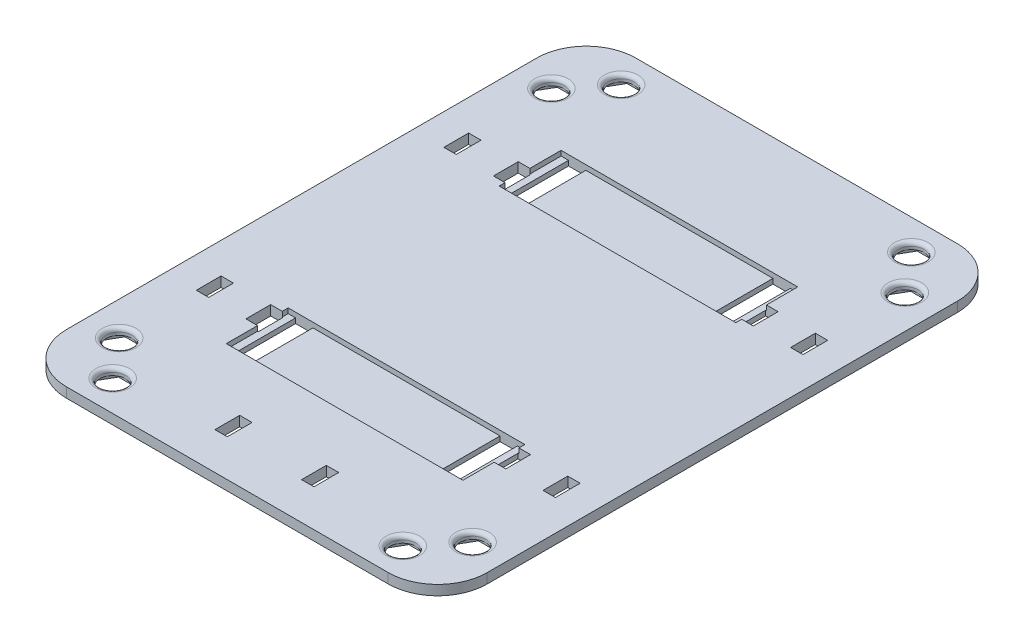
SolidWorks part; units mm, degrees
material "3-D Printed ABS"
ref_plane "Front Plane" through (0, 0, 0) normal (0, 0, 1) x (1, 0, 0)
ref_plane "Top Plane" through (0, 0, 0) normal (0, 1, 0) x (1, 0, 0)
ref_plane "Right Plane" through (0, 0, 0) normal (1, 0, 0) x (0, 0, -1)
sketch "Sketch1" plane through (0, 0, 0) normal (0, 1, 0) x (1, 0, 0)
  line L1 (-53.975, -73.025) -> (53.975, -73.025)
  line L2 (-53.975, -73.025) -> (-53.975, 73.025)
  line L3 (-53.975, 73.025) -> (53.975, 73.025)
  line L4 (53.975, -73.025) -> (53.975, 73.025)
  line L5 (-53.975, -73.025) -> (53.975, 73.025) construction
  line L6 (-53.975, 73.025) -> (53.975, -73.025) construction
  point P0 (0, 0)
  dimension "D1" = 107.95
  dimension "PlateY" = 146.05
extrude "Boss-Extrude1" add sketch "Sketch1" against normal blind 2.54
sketch "Sketch2" plane through (0, 0, 0) normal (0, 1, 0) x (1, 0, 0)
  line L0 (0, 0) -> (152.4, 0) construction
  line L1 (0, 0) -> (0, 152.4) construction
  line L4 (0, 0) -> (-53.975, 73.025) construction
  line L5 (0, 0) -> (-152.4, 0) construction
  line L6 (0, 0) -> (-152.4, 152.4) construction
  line L7 (-53.975, 73.025) -> (-53.975, -73.025) construction
  line L8 (53.975, 73.025) -> (-53.975, 73.025) construction
  line L9 (-152.4, 152.4) -> (-41.275, 60.325) construction
  line L10 (-41.275, 60.325) -> (0, 26.1257) construction
  line L11 (-30.7521, 73.025) -> (-53.975, 44.9974) construction
  circle A0 centre (-37.2189, 65.2108) radius 3.302
  circle A1 centre (45.3264, 55.4354) radius 3.302
  circle A2 centre (37.2189, 65.2108) radius 3.302
  circle A3 centre (-45.3264, -55.4354) radius 3.302
  circle A4 centre (-45.3264, 55.4354) radius 3.302
  circle A5 centre (-37.2189, -65.2108) radius 3.302
  circle A6 centre (37.2189, -65.2108) radius 3.302
  circle A7 centre (45.3264, -55.4354) radius 3.302
  point P12 (-41.275, 60.325)
  point P15 (-37.2189, 65.2108)
  dimension "D1" = 6.604
  dimension "D3" = 12.7
  dimension "D8" = 6.604
  dimension "D2" = 12.7
  dimension "D4" = 152.4
  dimension "D5" = 152.4
  dimension "D6" = 152.4
  dimension "D7" = 6.35
  dimension "D9" = 6.35
extrude "Cut-Extrude1" cut sketch "Sketch2" against normal through all
sketch "Sketch3" plane through (0, 0, 0) normal (0, 1, 0) x (1, 0, 0)
  line L0 (-53.975, 0) -> (53.975, 0) construction
  line L1 (-28.445, 42.9374) -> (-24, 42.9374)
  line L2 (-28.445, 42.9374) -> (-28.445, 27.0624)
  line L3 (-28.445, 27.0624) -> (-24, 27.0624)
  line L4 (-24, 42.9374) -> (-24, 27.0624)
  line L5 (24, 42.9374) -> (24, 27.0624)
  line L6 (28.445, 27.0624) -> (24, 27.0624)
  line L7 (28.445, 42.9374) -> (28.445, 27.0624)
  line L8 (28.445, 42.9374) -> (24, 42.9374)
  line L9 (-53.975, 73.025) -> (-53.975, -73.025) construction
  line L10 (53.975, -73.025) -> (53.975, 73.025) construction
  line L11 (0, -34.9999) -> (0, 79.6704) construction
  line L12 (0, 34.9999) -> (0, -79.6704) construction
  line L13 (28.445, -42.9374) -> (24, -42.9374)
  line L14 (28.445, -42.9374) -> (28.445, -27.0624)
  line L15 (28.445, -27.0624) -> (24, -27.0624)
  line L16 (24, -42.9374) -> (24, -27.0624)
  line L17 (-24, -42.9374) -> (-24, -27.0624)
  line L18 (-28.445, -27.0624) -> (-24, -27.0624)
  line L19 (-28.445, -42.9374) -> (-28.445, -27.0624)
  line L20 (-28.445, -42.9374) -> (-24, -42.9374)
  line L21 (-28.445, 34.9999) -> (-40.442, 34.9999) construction
  line L22 (-53.975, -73.025) -> (53.975, -73.025) construction
  point P31 (0, -73.025)
  point P32 (-53.975, 0)
  dimension "D1" = 15.875
  dimension "D2" = 4.445
  dimension "D3" = 24
  dimension "D4" = 34.9999
  dimension "D5" = 34.9999
extrude "Cut-Extrude2" cut sketch "Sketch3" against normal through all
fillet "Fillet1" radius 12.7 4 edges at (53.975, -1.27, -73.025) (53.975, -1.27, 73.025) (-53.975, -1.27, 73.025) (-53.975, -1.27, -73.025)
sketch "Sketch4" plane through (0, 0, 0) normal (0, 1, 0) x (1, 0, 0)
  line L0 (0, 0) -> (80.9727, -80.9727) construction
  line L1 (0, 0) -> (-80.9727, -80.9727) construction
  line L2 (69.1118, -51.1513) -> (28.7006, -10.7401)
  line L3 (28.7006, -10.7401) -> (10.7401, -28.7006)
  line L4 (10.7401, -28.7006) -> (51.1513, -69.1118)
  line L5 (51.1513, -69.1118) -> (69.1118, -51.1513)
  line L6 (0, 0) -> (0, -118.7381) construction
  line L7 (0, 0) -> (-98.4177, 0) construction
  line L8 (-51.1513, -69.1118) -> (-69.1118, -51.1513)
  line L9 (-69.1118, -51.1513) -> (-28.7006, -10.7401)
  line L10 (-28.7006, -10.7401) -> (-10.7401, -28.7006)
  line L11 (-10.7401, -28.7006) -> (-51.1513, -69.1118)
  line L12 (-69.1118, 51.1513) -> (-28.7006, 10.7401)
  line L13 (-51.1513, 69.1118) -> (-69.1118, 51.1513)
  line L14 (-10.7401, 28.7006) -> (-51.1513, 69.1118)
  line L15 (-28.7006, 10.7401) -> (-10.7401, 28.7006)
  line L16 (51.1513, 69.1118) -> (69.1118, 51.1513)
  line L17 (69.1118, 51.1513) -> (28.7006, 10.7401)
  line L18 (28.7006, 10.7401) -> (10.7401, 28.7006)
  line L19 (10.7401, 28.7006) -> (51.1513, 69.1118)
  point P6 (19.7204, -19.7204)
  dimension "D1" = 25.4
  dimension "D2" = 57.15
  dimension "D3" = 45
extrude "Cut-Extrude3" [suppressed] cut sketch "Sketch4" against normal blind 1.5875
sketch "Sketch6" [suppressed] plane through (0, 0, 0) normal (0, 1, 0) x (1, 0, 0)
  line L0 (46.3377, -44.1074) -> (34.6634, -32.4331) construction
  line L1 (0, 0) -> (0, -117.7376) construction
  line L2 (0, 0) -> (-151.7285, 0) construction
  line L4 (28.1601, -10.1996) -> (10.1996, -28.1601) construction
  line L5 (50.6107, -68.5712) -> (68.5712, -50.6107) construction
  text T0 "ESC" font "Century Gothic" height in points 22
  dimension "D1" = 45
  dimension "D2" = 20.32
  dimension "D3" = 20.32
extrude "Cut-Extrude5" [suppressed] cut sketch "Sketch6" against normal blind 3.175
sketch "Sketch5" plane through (0, 0, 0) normal (0, 1, 0) x (1, 0, 0)
  line L0 (41.275, 73.025) -> (-41.275, 73.025) construction
  line L1 (14.2875, 15.875) -> (-14.2875, 15.875)
  line L2 (14.2875, 15.875) -> (14.2875, 66.675)
  line L3 (14.2875, 66.675) -> (-14.2875, 66.675)
  line L4 (-14.2875, 15.875) -> (-14.2875, 66.675)
  point P4 (0, 15.875)
  dimension "D1" = 50.8
  dimension "D2" = 28.575
  dimension "D3" = 6.35
extrude "Cut-Extrude4" [suppressed] cut sketch "Sketch5" against normal blind 1.5875
ref_axis "Axis1" through (0, 0.3175, 0) along (0, -1, 0)
pattern_circular "CirPattern1" [suppressed] count 4 over 360 about axis through (0, 0.3175, 0) along (0, -1, 0) of bodies 105
sketch "Sketch7" plane through (0, 0, 0) normal (0, 1, 0) x (1, 0, 0)
  line L0 (0, 0) -> (0, -54.962) construction
  line L1 (63.4018, -13.3522) -> (38.0018, -13.3522)
  line L2 (63.4018, -13.3522) -> (63.4018, 43.7978)
  line L3 (63.4018, 43.7978) -> (38.0018, 43.7978)
  line L4 (38.0018, -13.3522) -> (38.0018, 43.7978)
  line L5 (-38.0018, -13.3522) -> (-38.0018, 43.7978)
  line L6 (-63.4018, 43.7978) -> (-38.0018, 43.7978)
  line L7 (-63.4018, -13.3522) -> (-63.4018, 43.7978)
  line L8 (-63.4018, -13.3522) -> (-38.0018, -13.3522)
  line L9 (-41.275, -73.025) -> (41.275, -73.025) construction
  line L10 (38.5677, -40.64) -> (-18.5823, -40.64)
  line L11 (38.5677, -40.64) -> (38.5677, -66.04)
  line L12 (38.5677, -66.04) -> (-18.5823, -66.04)
  line L13 (-18.5823, -40.64) -> (-18.5823, -66.04)
  line L14 (38.5677, -40.64) -> (-18.5823, -66.04) construction
  line L15 (38.5677, -66.04) -> (-18.5823, -40.64) construction
  line L16 (19.844, -36.1003) -> (-37.306, -36.1003)
  line L17 (19.844, -36.1003) -> (19.844, -61.5003)
  line L18 (19.844, -61.5003) -> (-37.306, -61.5003)
  line L19 (-37.306, -36.1003) -> (-37.306, -61.5003)
  line L20 (19.844, -36.1003) -> (-37.306, -61.5003) construction
  line L21 (19.844, -61.5003) -> (-37.306, -36.1003) construction
  point P11 (9.9927, -53.34)
  point P18 (-8.731, -48.8003)
  dimension "D1" = 57.15
  dimension "D2" = 25.4
  dimension "D3" = 57.15
  dimension "D4" = 25.4
  dimension "D5" = 6.985
  dimension "D6" = 57.15
  dimension "D7" = 25.4
extrude "Cut-Extrude6" [suppressed] cut sketch "Sketch7" against normal blind 1.27
sketch "Sketch8" plane through (0, 0, 0) normal (0, 1, 0) x (1, 0, 0)
  line L7 (19.05, -31.75) -> (-19.05, -31.75)
  line L8 (19.05, -31.75) -> (19.05, 31.75)
  line L9 (19.05, 31.75) -> (-19.05, 31.75)
  line L10 (-19.05, -31.75) -> (-19.05, 31.75)
  point P0 (0, 0)
  dimension "D1" = 38.1
  dimension "D2" = 31.75
  dimension "D3" = 63.5
extrude "Boss-Extrude3" [suppressed] add sketch "Sketch8" along normal blind 2.54
sketch "Sketch11" plane through (0, 0, 0) normal (0, 1, 0) x (1, 0, 0)
  line L0 (-28.445, -42.9374) -> (-24, -42.9374) construction
  line L1 (30.35, -42.9374) -> (-30.35, -42.9374)
  line L2 (30.35, -42.9374) -> (30.35, -27.0624)
  line L3 (30.35, -27.0624) -> (-30.35, -27.0624)
  line L4 (-30.35, -42.9374) -> (-30.35, -27.0624)
  line L5 (28.445, -27.0624) -> (24, -27.0624) construction
  line L6 (28.445, -42.9374) -> (28.445, -27.0624) construction
  line L7 (-28.445, -27.0624) -> (-28.445, -42.9374) construction
  line L8 (0, 0) -> (90.9737, 0) construction
  line L9 (-30.35, 42.9374) -> (-30.35, 27.0624)
  line L10 (30.35, 27.0624) -> (-30.35, 27.0624)
  line L11 (30.35, 42.9374) -> (30.35, 27.0624)
  line L12 (30.35, 42.9374) -> (-30.35, 42.9374)
  dimension "D1" = 1.905
  dimension "D2" = 1.905
extrude "Cut-Extrude9" cut sketch "Sketch11" against normal mid plane 2.54
sketch "Sketch12" plane through (0, 0, 0) normal (0, 1, 0) x (1, 0, 0)
  line L1 (12.7, -51.1354) -> (-12.7, -51.1354)
  line L2 (12.7, -51.1354) -> (12.7, -34.9999)
  line L3 (12.7, -34.9999) -> (-12.7, -34.9999)
  line L4 (-12.7, -51.1354) -> (-12.7, -34.9999)
  line L6 (23.8125, 0) -> (-23.8125, 0) construction
  line L7 (-53.975, 60.325) -> (-53.975, -60.325) construction
  line L9 (-12.7, 51.1354) -> (-12.7, 34.9999)
  line L10 (12.7, 34.9999) -> (-12.7, 34.9999)
  line L11 (12.7, 51.1354) -> (12.7, 34.9999)
  line L12 (12.7, 51.1354) -> (-12.7, 51.1354)
  point P6 (-53.975, 0)
  dimension "D1" = 25.4
  dimension "D2" = 34.9999
extrude "Cut-Extrude12" [suppressed] cut sketch "Sketch12" along normal through all
sketch "Sketch9" plane through (0, 0, 0) normal (0, 1, 0) x (1, 0, 0)
  line L1 (25.1579, -52.4084) -> (-25.6421, -52.4084)
  line L2 (25.1579, -52.4084) -> (25.1579, -1.6084)
  line L3 (25.1579, -1.6084) -> (-25.6421, -1.6084)
  line L4 (-25.6421, -52.4084) -> (-25.6421, -1.6084)
  line L5 (25.1579, -52.4084) -> (-25.6421, -1.6084) construction
  line L6 (25.1579, -1.6084) -> (-25.6421, -52.4084) construction
  point P0 (-0.2421, -27.0084)
  dimension "D1" = 50.8
  dimension "D2" = 50.8
sketch "Sketch13" plane through (0, 0, 0) normal (0, 1, 0) x (1, 0, 0)
  line L0 (0, 0) -> (0, -106.7514) construction
  line L1 (34.925, 3.175) -> (28.575, 3.175)
  line L2 (34.925, 3.175) -> (34.925, -3.175)
  line L3 (34.925, -3.175) -> (28.575, -3.175)
  line L4 (28.575, 3.175) -> (28.575, -3.175)
  line L5 (34.925, 3.175) -> (28.575, -3.175) construction
  line L6 (34.925, -3.175) -> (28.575, 3.175) construction
  line L7 (-34.925, -3.175) -> (-28.575, 3.175) construction
  line L8 (-34.925, 3.175) -> (-28.575, -3.175) construction
  line L9 (-28.575, 3.175) -> (-28.575, -3.175)
  line L10 (-34.925, -3.175) -> (-28.575, -3.175)
  line L11 (-34.925, 3.175) -> (-34.925, -3.175)
  line L12 (-34.925, 3.175) -> (-28.575, 3.175)
  point P0 (31.75, 0)
  point P12 (-31.75, 0)
  dimension "D1" = 6.35
  dimension "D2" = 28.575
  dimension "D3" = 0
extrude "Cut-Extrude13" [suppressed] cut sketch "Sketch13" against normal through all
fillet "Fillet2" radius 1.016 8 edges at (-37.2189, 0, -61.9088) (37.2189, 0, 68.5128) (45.3264, 0, 58.7374) (-37.2189, 0, 61.9088) (-45.3264, 0, 52.1334) (45.3264, 0, -58.7374) (37.2189, 0, -68.5128) (-45.3264, 0, -52.1334)
sketch "Sketch14" plane through (0, 0, 0) normal (0, 1, 0) x (1, 0, 0)
  line L0 (0, 76.698) -> (0, -76.698) construction
  line L1 (33.3248, -34.925) -> (30.1498, -34.925)
  line L2 (33.3248, -34.925) -> (33.3248, -28.575)
  line L3 (33.3248, -28.575) -> (30.1498, -28.575)
  line L4 (30.1498, -34.925) -> (30.1498, -28.575)
  line L5 (0, 0) -> (-92.4571, 0) construction
  line L6 (-30.1498, -34.925) -> (-30.1498, -28.575)
  line L7 (-33.3248, -28.575) -> (-30.1498, -28.575)
  line L8 (-33.3248, -34.925) -> (-33.3248, -28.575)
  line L9 (-33.3248, -34.925) -> (-30.1498, -34.925)
  line L10 (-33.3248, 34.925) -> (-30.1498, 34.925)
  line L11 (-33.3248, 34.925) -> (-33.3248, 28.575)
  line L12 (-33.3248, 28.575) -> (-30.1498, 28.575)
  line L13 (-30.1498, 34.925) -> (-30.1498, 28.575)
  line L14 (30.1498, 34.925) -> (30.1498, 28.575)
  line L15 (33.3248, 28.575) -> (30.1498, 28.575)
  line L16 (33.3248, 34.925) -> (33.3248, 28.575)
  line L17 (33.3248, 34.925) -> (30.1498, 34.925)
  line L18 (-41.275, -73.025) -> (41.275, -73.025) construction
  line L19 (-9.525, -63.5) -> (-9.525, -57.15)
  line L20 (12.7, -63.5) -> (9.525, -63.5)
  line L21 (12.7, -63.5) -> (12.7, -57.15)
  line L22 (12.7, -57.15) -> (9.525, -57.15)
  line L23 (38.1, -73.025) -> (38.1, 73.025) construction
  line L24 (41.275, 73.025) -> (-41.275, 73.025) construction
  line L25 (42.8752, 34.925) -> (46.0502, 34.925)
  line L26 (42.8752, 34.925) -> (42.8752, 28.575)
  line L27 (42.8752, 28.575) -> (46.0502, 28.575)
  line L28 (46.0502, 34.925) -> (46.0502, 28.575)
  line L29 (46.0502, -34.925) -> (46.0502, -28.575)
  line L30 (42.8752, -28.575) -> (46.0502, -28.575)
  line L31 (42.8752, -34.925) -> (42.8752, -28.575)
  line L32 (42.8752, -34.925) -> (46.0502, -34.925)
  line L33 (-46.0502, 34.925) -> (-46.0502, 28.575)
  line L34 (-42.8752, 28.575) -> (-46.0502, 28.575)
  line L35 (-42.8752, 34.925) -> (-42.8752, 28.575)
  line L36 (-42.8752, 34.925) -> (-46.0502, 34.925)
  line L37 (-42.8752, -34.925) -> (-46.0502, -34.925)
  line L38 (-42.8752, -34.925) -> (-42.8752, -28.575)
  line L39 (-42.8752, -28.575) -> (-46.0502, -28.575)
  line L40 (-46.0502, -34.925) -> (-46.0502, -28.575)
  line L41 (53.975, -50.8) -> (-53.975, -50.8) construction
  line L42 (53.975, -60.325) -> (53.975, 60.325) construction
  line L43 (-53.975, 60.325) -> (-53.975, -60.325) construction
  line L44 (0, -178.298) -> (0, -24.902) construction
  line L45 (9.525, -63.5) -> (9.525, -57.15)
  line L46 (-12.7, -57.15) -> (-9.525, -57.15)
  line L47 (-12.7, -63.5) -> (-12.7, -57.15)
  line L48 (-12.7, -63.5) -> (-9.525, -63.5)
  dimension "D2" = 3.175
  dimension "D3" = 6.35
  dimension "D4" = 28.575
  dimension "D5" = 3.175
  dimension "D6" = 6.35
  dimension "D7" = 9.525
  dimension "D8" = 9.525
  dimension "D9" = 38.1
  dimension "D10" = 22.225
  dimension "D11" = 30.1498
extrude "Cut-Extrude14" cut sketch "Sketch14" against normal through all
sketch "Sketch17" plane through (0, -2.54, 0) normal (0, -1, 0) x (1, 0, 0)
  line L0 (0, 0) -> (-152.4, 0) construction
  line L1 (0, 0) -> (0, -152.4) construction
  line L2 (0, -152.4) -> (-152.4, -152.4) construction
  line L3 (-152.4, -152.4) -> (-152.4, 0) construction
  line L4 (-152.4, -152.4) -> (0, 0) construction
  line L5 (41.275, -73.025) -> (-41.275, -73.025) construction
  line L6 (-53.975, -60.325) -> (-53.975, 60.325) construction
  line L7 (-152.4, -152.4) -> (-41.275, -60.325) construction
  line L8 (-41.275, -60.325) -> (0, -26.1257) construction
  line L9 (43.2734, -51.8794) -> (47.3795, -51.8794)
  line L10 (-41.2203, -55.4354) -> (-43.2734, -51.8794)
  line L11 (-43.2734, -51.8794) -> (-47.3795, -51.8794)
  line L12 (-47.3795, -51.8794) -> (-49.4325, -55.4354)
  line L13 (-49.4325, -55.4354) -> (-47.3795, -58.9914)
  line L14 (-47.3795, -58.9914) -> (-43.2734, -58.9914)
  line L15 (-43.2734, -58.9914) -> (-41.2203, -55.4354)
  line L16 (-33.1128, -65.2108) -> (-35.1659, -61.6548)
  line L17 (-35.1659, -61.6548) -> (-39.272, -61.6548)
  line L18 (-39.272, -61.6548) -> (-41.3251, -65.2108)
  line L19 (-41.3251, -65.2108) -> (-39.272, -68.7668)
  line L20 (-39.272, -68.7668) -> (-35.1659, -68.7668)
  line L21 (-35.1659, -68.7668) -> (-33.1128, -65.2108)
  line L22 (47.3795, -51.8794) -> (49.4325, -55.4354)
  line L23 (49.4325, -55.4354) -> (47.3795, -58.9914)
  line L24 (41.2203, -55.4354) -> (43.2734, -51.8794)
  line L25 (43.2734, -58.9914) -> (41.2203, -55.4354)
  line L26 (47.3795, -58.9914) -> (43.2734, -58.9914)
  line L27 (35.1659, -61.6548) -> (39.272, -61.6548)
  line L28 (33.1128, -65.2108) -> (35.1659, -61.6548)
  line L29 (39.272, -61.6548) -> (41.3251, -65.2108)
  line L30 (41.3251, -65.2108) -> (39.272, -68.7668)
  line L31 (35.1659, -68.7668) -> (33.1128, -65.2108)
  line L32 (39.272, -68.7668) -> (35.1659, -68.7668)
  line L33 (-41.2203, 55.4354) -> (-43.2734, 51.8794)
  line L34 (-43.2734, 51.8794) -> (-47.3795, 51.8794)
  line L35 (-47.3795, 51.8794) -> (-49.4325, 55.4354)
  line L36 (-49.4325, 55.4354) -> (-47.3795, 58.9914)
  line L37 (-47.3795, 58.9914) -> (-43.2734, 58.9914)
  line L38 (-43.2734, 58.9914) -> (-41.2203, 55.4354)
  line L39 (-33.1128, 65.2108) -> (-35.1659, 61.6548)
  line L40 (-35.1659, 61.6548) -> (-39.272, 61.6548)
  line L41 (-39.272, 61.6548) -> (-41.3251, 65.2108)
  line L42 (-41.3251, 65.2108) -> (-39.272, 68.7668)
  line L43 (-39.272, 68.7668) -> (-35.1659, 68.7668)
  line L44 (-35.1659, 68.7668) -> (-33.1128, 65.2108)
  line L45 (39.272, 68.7668) -> (35.1659, 68.7668)
  line L46 (35.1659, 68.7668) -> (33.1128, 65.2108)
  line L47 (41.3251, 65.2108) -> (39.272, 68.7668)
  line L48 (39.272, 61.6548) -> (41.3251, 65.2108)
  line L49 (33.1128, 65.2108) -> (35.1659, 61.6548)
  line L50 (35.1659, 61.6548) -> (39.272, 61.6548)
  line L51 (47.3795, 58.9914) -> (43.2734, 58.9914)
  line L52 (43.2734, 58.9914) -> (41.2203, 55.4354)
  line L53 (41.2203, 55.4354) -> (43.2734, 51.8794)
  line L54 (49.4325, 55.4354) -> (47.3795, 58.9914)
  line L55 (47.3795, 51.8794) -> (49.4325, 55.4354)
  line L56 (43.2734, 51.8794) -> (47.3795, 51.8794)
  circle A0 centre (-45.3264, -55.4354) radius 3.556 construction
  circle A1 centre (-37.2189, -65.2108) radius 3.556 construction
  point P0 (0, 0)
  point P6 (-41.275, -60.2488)
  dimension "D1" = 12.7762
  dimension "D2" = 12.7
  dimension "D3" = 7.112
  dimension "D4" = 7.112
extrude "Cut-Extrude15" cut sketch "Sketch17" against normal blind 0.7937
equation "\"Plate Dim Y\"= \"Plate Dim Y@Quad Assemb.SLDASM\""
equation "\"PlateY@Sketch1\" = \"Plate Dim Y\""
equation "\"D1@Sketch1\"= \"Plate Dim X\""
equation "\"D1@Boss-Extrude1\" = \"Plate Thickness\""
equation "\"Plate Dim X\"= \"Plate Dim X@Quad Assemb.SLDASM\""
equation "\"Plate Thickness\"= \"Plate Thickness@Quad Assemb.sldasm\""
equation "\"Batt X\"= \"Batt X@Quad Assemb.sldasm\""
equation "\"Batt Y\"= \"Batt Y@Quad Assemb.sldasm\""
equation "\"D3@Sketch3\"=\"Batt X\"/2"
equation "\"D4@Sketch3\"=\"Batt Y\"/4"
equation "\"D5@Sketch3\"=\"Batt Y\"*2/8"
equation "\"Dowell Width\"= \"Dowell Width@Quad Assemb.sldasm\""
equation "\"D1@Sketch2\"=\"Dowell Width\"+.01"
equation "\"D2@Sketch12\"=\"Batt Y\"/4"
equation "\"D7@Sketch2\"=\"Dowell Width\""
equation "\"D8@Sketch2\"=\"Dowell Width\" +0.01in"
equation "\"D9@Sketch2\"=\"Dowell Width\""
